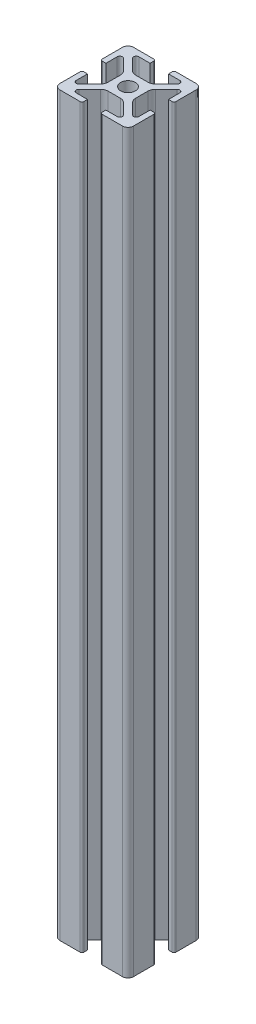
SolidWorks part; units mm, degrees
ref_plane "Plan de face" through (0, 0, 0) normal (0, 0, 1) x (1, 0, 0)
ref_plane "Plan de dessus" through (0, 0, 0) normal (0, 1, 0) x (1, 0, 0)
ref_plane "Plan de droite" through (0, 0, 0) normal (1, 0, 0) x (0, 0, -1)
sketch "Esquisse1" plane through (0, 0, 0) normal (0, 1, 0) x (1, 0, 0)
  line L0 (-5.6497, 11.1927) -> (14.3503, 11.1927) construction
  line L1 (14.3503, 11.1927) -> (14.3503, -8.8073) construction
  line L2 (14.3503, -8.8073) -> (-5.6497, -8.8073) construction
  line L3 (-5.6497, -8.8073) -> (-5.6497, 11.1927) construction
  line L4 (-5.6497, 11.1927) -> (14.3503, -8.8073) construction
  line L5 (-5.6497, -8.8073) -> (14.3503, 11.1927) construction
  line L6 (-5.6497, 9.6927) -> (-5.6497, 4.1927)
  line L7 (-5.1497, 3.6927) -> (-4.1497, 3.6927)
  line L8 (-4.1497, 3.6927) -> (-4.1497, 6.7528)
  line L9 (-2.9547, 7.2478) -> (0.0145, 4.2785)
  line L10 (0.6003, 2.8643) -> (0.6003, -0.4788)
  line L11 (0.0145, -1.8931) -> (-2.9547, -4.8623)
  line L12 (-4.1497, -4.3673) -> (-4.1497, -1.3073)
  line L13 (-4.1497, -1.3073) -> (-5.1497, -1.3073)
  line L14 (-5.6497, -1.8073) -> (-5.6497, -7.3073)
  line L15 (-4.1497, -8.8073) -> (1.3503, -8.8073)
  line L16 (1.8503, -8.3073) -> (1.8503, -7.3073)
  line L17 (1.8503, -7.3073) -> (-1.2098, -7.3073)
  line L18 (-1.7047, -6.1123) -> (1.2645, -3.1431)
  line L19 (2.6787, -2.5573) -> (6.0219, -2.5573)
  line L20 (7.4361, -3.1431) -> (10.4053, -6.1123)
  line L21 (9.9103, -7.3073) -> (6.8503, -7.3073)
  line L22 (6.8503, -7.3073) -> (6.8503, -8.3073)
  line L23 (7.3503, -8.8073) -> (12.8503, -8.8073)
  line L24 (14.3503, -7.3073) -> (14.3503, -1.8073)
  line L25 (13.8503, -1.3073) -> (12.8503, -1.3073)
  line L26 (12.8503, -1.3073) -> (12.8503, -4.3673)
  line L27 (11.6553, -4.8623) -> (8.6861, -1.8931)
  line L28 (8.1003, -0.4788) -> (8.1003, 2.8643)
  line L29 (8.6861, 4.2785) -> (11.6553, 7.2478)
  line L30 (12.8503, 6.7528) -> (12.8503, 3.6927)
  line L31 (12.8503, 3.6927) -> (13.8503, 3.6927)
  line L32 (14.3503, 4.1927) -> (14.3503, 9.6927)
  line L33 (12.8503, 11.1927) -> (7.3503, 11.1927)
  line L34 (6.8503, 10.6927) -> (6.8503, 9.6927)
  line L35 (6.8503, 9.6927) -> (9.9103, 9.6927)
  line L36 (10.4053, 8.4978) -> (7.4361, 5.5285)
  line L37 (6.0219, 4.9427) -> (2.6787, 4.9427)
  line L38 (1.2645, 5.5285) -> (-1.7047, 8.4978)
  line L39 (-1.2098, 9.6927) -> (1.8503, 9.6927)
  line L40 (1.8503, 9.6927) -> (1.8503, 10.6927)
  line L41 (1.3503, 11.1927) -> (-4.1497, 11.1927)
  line L42 (-4.1497, -6.0573) -> (-2.8997, -7.3073) construction
  line L43 (0.6003, -1.3073) -> (1.8503, -2.5573) construction
  line L44 (0.6003, 3.6927) -> (1.8503, 4.9427) construction
  line L45 (-4.1497, 8.4427) -> (-2.8997, 9.6927) construction
  line L46 (12.8503, 8.4427) -> (11.6003, 9.6927) construction
  line L47 (8.1003, 3.6927) -> (6.8503, 4.9427) construction
  line L48 (12.8503, -6.0573) -> (11.6003, -7.3073) construction
  line L49 (8.1003, -1.3073) -> (6.8503, -2.5573) construction
  line L50 (8.1003, 1.1927) -> (0.6003, 1.1927) construction
  line L51 (0.6003, 1.1927) -> (4.3503, 4.9427) construction
  line L52 (4.3503, 4.9427) -> (4.3503, -2.5573) construction
  arc A0 (14.3503, 9.6927) -> (12.8503, 11.1927) centre (12.8503, 9.6927) ccw
  arc A1 (12.8503, -8.8073) -> (14.3503, -7.3073) centre (12.8503, -7.3073) ccw
  arc A2 (-5.6497, -7.3073) -> (-4.1497, -8.8073) centre (-4.1497, -7.3073) ccw
  arc A3 (-5.6497, 9.6927) -> (-4.1497, 11.1927) centre (-4.1497, 9.6927) cw
  arc A4 (-2.9547, -4.8623) -> (-4.1497, -4.3673) centre (-3.4497, -4.3673) cw
  arc A5 (-1.2098, -7.3073) -> (-1.7047, -6.1123) centre (-1.2098, -6.6073) cw
  arc A6 (10.4053, -6.1123) -> (9.9103, -7.3073) centre (9.9103, -6.6073) cw
  arc A7 (12.8503, -4.3673) -> (11.6553, -4.8623) centre (12.1503, -4.3673) cw
  arc A8 (11.6553, 7.2478) -> (12.8503, 6.7528) centre (12.1503, 6.7528) cw
  arc A9 (9.9103, 9.6927) -> (10.4053, 8.4978) centre (9.9103, 8.9927) cw
  arc A10 (-1.7047, 8.4978) -> (-1.2098, 9.6927) centre (-1.2098, 8.9927) cw
  arc A11 (-4.1497, 6.7528) -> (-2.9547, 7.2478) centre (-3.4497, 6.7528) cw
  arc A12 (14.3503, -1.8073) -> (13.8503, -1.3073) centre (13.8503, -1.8073) ccw
  arc A13 (13.8503, 3.6927) -> (14.3503, 4.1927) centre (13.8503, 4.1927) ccw
  arc A14 (7.3503, 11.1927) -> (6.8503, 10.6927) centre (7.3503, 10.6927) ccw
  arc A15 (1.8503, 10.6927) -> (1.3503, 11.1927) centre (1.3503, 10.6927) ccw
  arc A16 (-5.6497, 4.1927) -> (-5.1497, 3.6927) centre (-5.1497, 4.1927) ccw
  arc A17 (-5.1497, -1.3073) -> (-5.6497, -1.8073) centre (-5.1497, -1.8073) ccw
  arc A18 (1.3503, -8.8073) -> (1.8503, -8.3073) centre (1.3503, -8.3073) ccw
  arc A19 (6.8503, -8.3073) -> (7.3503, -8.8073) centre (7.3503, -8.3073) ccw
  arc A20 (6.0219, -2.5573) -> (7.4361, -3.1431) centre (6.0219, -4.5573) cw
  arc A21 (0.0145, 4.2785) -> (0.6003, 2.8643) centre (-1.3997, 2.8643) cw
  arc A22 (0.6003, -0.4788) -> (0.0145, -1.8931) centre (-1.3997, -0.4788) cw
  arc A23 (1.2645, -3.1431) -> (2.6787, -2.5573) centre (2.6787, -4.5573) cw
  arc A24 (8.1003, 2.8643) -> (8.6861, 4.2785) centre (10.1003, 2.8643) cw
  arc A25 (8.6861, -1.8931) -> (8.1003, -0.4788) centre (10.1003, -0.4788) cw
  arc A26 (7.4361, 5.5285) -> (6.0219, 4.9427) centre (6.0219, 6.9427) cw
  arc A27 (2.6787, 4.9427) -> (1.2645, 5.5285) centre (2.6787, 6.9427) cw
  circle A28 centre (4.3503, 1.1927) radius 2
  point P125 (14.3503, -1.3073)
  point P128 (14.3503, 3.6927)
  point P131 (6.8503, 11.1927)
  point P134 (1.8503, 11.1927)
  point P137 (-5.6497, 3.6927)
  point P140 (-5.6497, -1.3073)
  point P143 (1.8503, -8.8073)
  point P146 (6.8503, -8.8073)
  dimension "D33" = 1.5
  dimension "D34" = 0.7
  dimension "D35" = 0.5
  dimension "D36" = 2
  dimension "D1" = 20
  dimension "D2" = 20
  dimension "D3" = 7.5
  dimension "D4" = 7.5
  dimension "7.5" = 7.5
  dimension "D5" = 7.5
  dimension "D6" = 7.5
  dimension "D7" = 7.5
  dimension "D8" = 7.5
  dimension "D9" = 7.5
  dimension "D10" = 7.5
  dimension "D11" = 7.5
  dimension "D12" = 270
  dimension "D13" = 5
  dimension "D14" = 5
  dimension "D15" = 5
  dimension "D16" = 5
  dimension "D17" = 90
  dimension "D18" = 90
  dimension "D19" = 1.5
  dimension "D20" = 135
  dimension "D21" = 1.5
  dimension "D22" = 135
  dimension "D23" = 1.5
  dimension "D24" = 1.5
  dimension "D25" = 1.5
  dimension "D26" = 1.5
  dimension "D27" = 1.5
  dimension "D28" = 90
  dimension "D29" = 90
  dimension "D30" = 90
  dimension "D31" = 90
  dimension "D32" = 90
extrude "Boss.-Extru.1" add sketch "Esquisse1" along normal blind 200
